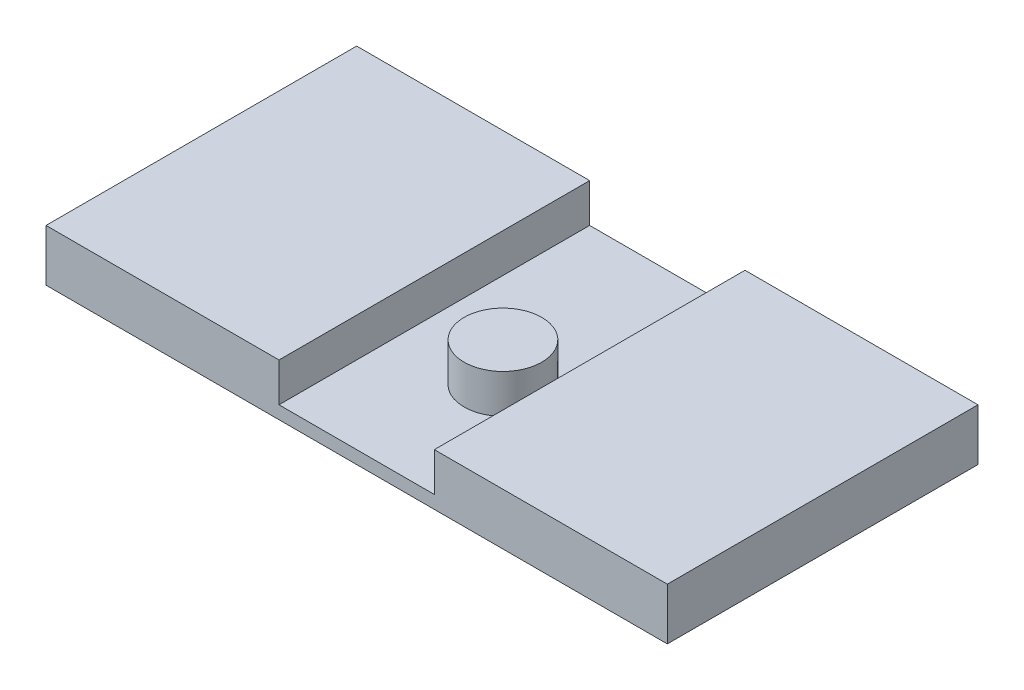
SolidWorks part; units mm, degrees
ref_plane "Front Plane" through (0, 0, 0) normal (0, 0, 1) x (1, 0, 0)
ref_plane "Top Plane" through (0, 0, 0) normal (0, 1, 0) x (1, 0, 0)
ref_plane "Right Plane" through (0, 0, 0) normal (1, 0, 0) x (0, 0, -1)
sketch "Sketch1" plane through (0, 0, 0) normal (0, 1, 0) x (1, 0, 0)
  line L1 (-152.4, -76.2) -> (152.4, -76.2)
  line L2 (-152.4, -76.2) -> (-152.4, 76.2)
  line L3 (-152.4, 76.2) -> (152.4, 76.2)
  line L4 (152.4, -76.2) -> (152.4, 76.2)
  line L5 (-152.4, -76.2) -> (152.4, 76.2) construction
  line L6 (-152.4, 76.2) -> (152.4, -76.2) construction
  point P0 (0, 0)
  dimension "D1" = 152.4
  dimension "D2" = 304.8
extrude "Boss-Extrude1" add sketch "Sketch1" along normal blind 25.4
sketch "Sketch2" plane through (0, 25.4, 0) normal (0, 1, 0) x (-1, 0, 0)
  line L1 (38.1, -76.2) -> (-38.1, -76.2)
  line L2 (38.1, -76.2) -> (38.1, 76.2)
  line L3 (38.1, 76.2) -> (-38.1, 76.2)
  line L4 (-38.1, -76.2) -> (-38.1, 76.2)
  line L5 (38.1, -76.2) -> (-38.1, 76.2) construction
  line L6 (38.1, 76.2) -> (-38.1, -76.2) construction
  point P0 (0, 0)
  dimension "D1" = 152.4
  dimension "D2" = 76.2
extrude "Cut-Extrude1" cut sketch "Sketch2" against normal blind 19.05
sketch "Sketch3" plane through (0, 6.35, 0) normal (0, 1, 0) x (-1, 0, 0)
  line L0 (38.1, 76.2) -> (-38.1, 76.2) construction
  circle A0 centre (-8.255, 12.7) radius 19.05
  dimension "D1" = 38.1
  dimension "D2" = 63.5
  dimension "D3" = 46.355
extrude "Boss-Extrude2" add sketch "Sketch3" along normal blind 19.05
sketch "Sketch4" plane through (0, 6.35, 0) normal (0, 1, 0) x (1, 0, 0)
  circle A0 centre (8.255, -12.7) radius 19.685
  circle A1 centre (8.255, -12.7) radius 19.05 construction
  dimension "D1" = 39.37
